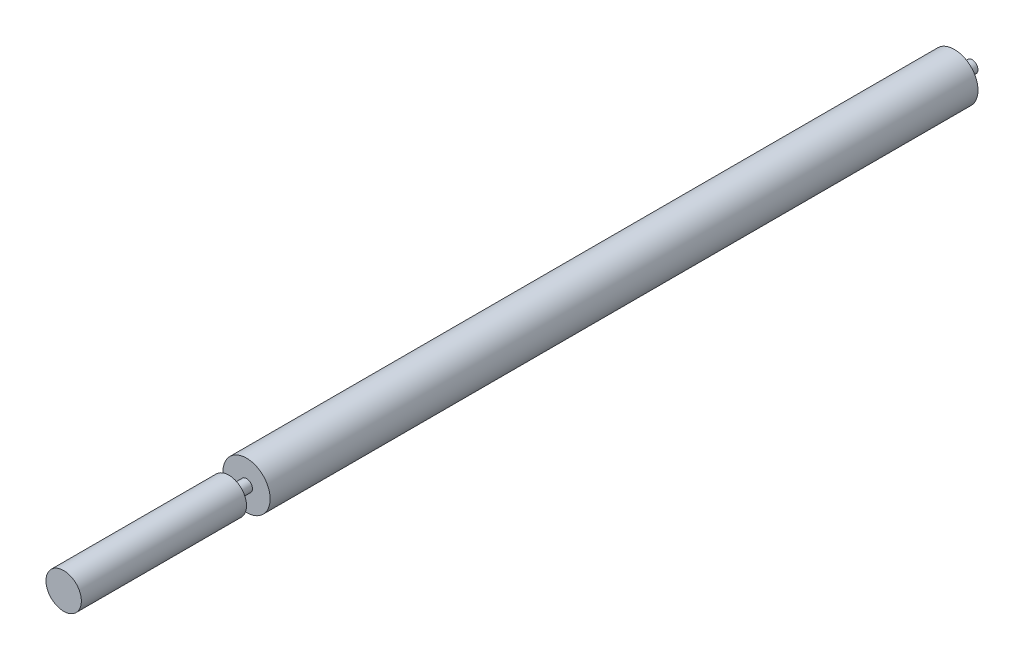
SolidWorks part; units mm, degrees
material "AISI 1035 Steel (SS)"
ref_plane "Front Plane" through (0, 0, 0) normal (0, 0, 1) x (1, 0, 0)
ref_plane "Top Plane" through (0, 0, 0) normal (0, 1, 0) x (1, 0, 0)
ref_plane "Right Plane" through (0, 0, 0) normal (1, 0, 0) x (0, 0, -1)
sketch "Sketch1" plane through (0, 0, 0) normal (0, 0, 1) x (1, 0, 0)
  circle A0 centre (0, 0) radius 25.4
  circle A1 centre (0, 0) radius 6.35
  dimension "D1" = 50.8
  dimension "D2" = 12.7
extrude "Boss-Extrude1" add sketch "Sketch1" along normal mid plane 800.1 contours A1 region at (0, 0, 0)
extrude "Boss-Extrude2" add sketch "Sketch1<3>" along normal mid plane 762
sketch "Sketch1<3>" plane through (0, 0, 0) normal (0, 0, 1) x (1, 0, 0) same geometry as "Sketch1"
sketch "Sketch2" plane through (0, 0, 0) normal (1, 0, 0) x (0, 0, -1)
  circle A0 centre (-129.0159, 11.7601) radius 15.13
sketch "Sketch3" plane through (0, 0, 381) normal (0, 0, 1) x (1, 0, 0)
  circle A0 centre (0, 0) radius 19.05
  dimension "D1" = 38.1
extrude "Boss-Extrude3" add sketch "Sketch3" along normal blind 177.8 from offset 19.05
